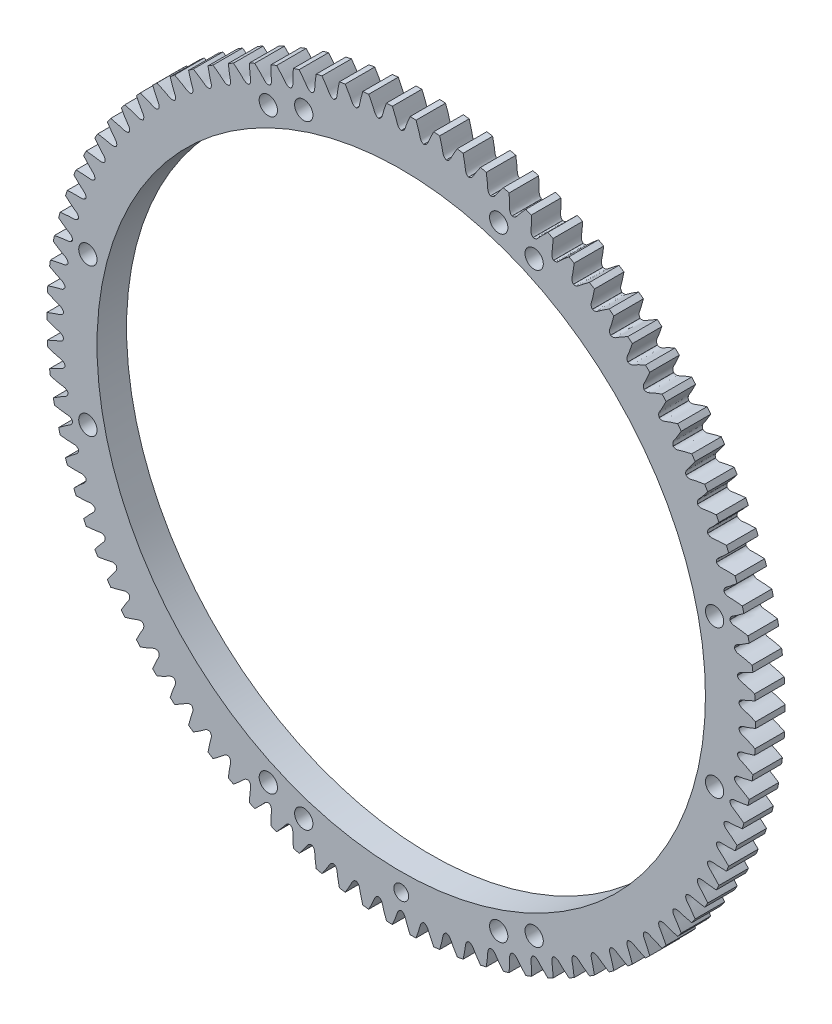
SolidWorks part; units mm, degrees
ref_plane "前视基准面" through (0, 0, 0) normal (0, 0, 1) x (1, 0, 0)
ref_plane "上视基准面" through (0, 0, 0) normal (0, 1, 0) x (1, 0, 0)
ref_plane "右视基准面" through (0, 0, 0) normal (1, 0, 0) x (0, 0, -1)
other "Configuration Table"
sketch "草图1" plane through (0, 0, 0) normal (0, 0, 1) x (1, 0, 0)
  circle A0 centre (0, 0) radius 60
ref_axis "基准轴1" through (0, 0, -66) along (0, 0, 1)
sketch "草图2" plane through (0, 0, 0) normal (0, 0, 1) x (1, 0, 0)
  line L0 (0, 0) -> (0, 60) construction
  circle A0 centre (0, 0) radius 60 construction
  arc A1 (0.01, 57.1863) -> (-0.01, 57.1863) centre (0, 0) ccw
  arc A2 (6.9854, 68.0885) -> (-6.9854, 68.0885) centre (0, 0) ccw
  spline S0 degree 3 poles (0.01, 57.1863) (0.5475, 57.3458) (0.6685, 57.9002) (0.9065, 58.5435) (1.0486, 58.9183) (1.2076, 59.31) (1.3828, 59.7189) (1.5753, 60.1443) (1.7858, 60.5857) (2.0149, 61.0426) (2.2635, 61.5143) (2.5321, 62.0003) (2.8214, 62.5) (3.1321, 63.0126) (3.4648, 63.5376) (3.8201, 64.0743) (4.1987, 64.6219) (4.601, 65.1797) (5.0277, 65.747) (5.4793, 66.3231) (6.1245, 67.1132) (6.6336, 67.6992) (6.9854, 68.0885) knots 0 0 0 0 0.098237 0.127249 0.157953 0.190349 0.224438 0.260219 0.297692 0.336857 0.377715 0.420265 0.464507 0.510441 0.558068 0.607386 0.658397 0.711101 0.765496 0.821584 0.879364 1 1 1 1
  spline S1 degree 3 poles (-0.01, 57.1863) (-0.5475, 57.3458) (-0.6685, 57.9002) (-0.9065, 58.5435) (-1.0486, 58.9183) (-1.2076, 59.31) (-1.3828, 59.7189) (-1.5753, 60.1443) (-1.7858, 60.5857) (-2.0149, 61.0426) (-2.2635, 61.5143) (-2.5321, 62.0003) (-2.8214, 62.5) (-3.1321, 63.0126) (-3.4648, 63.5376) (-3.8201, 64.0743) (-4.1987, 64.6219) (-4.601, 65.1797) (-5.0277, 65.747) (-5.4793, 66.3231) (-6.1245, 67.1132) (-6.6336, 67.6992) (-6.9854, 68.0885) knots 0 0 0 0 0.098237 0.127249 0.157953 0.190349 0.224438 0.260219 0.297692 0.336857 0.377715 0.420265 0.464507 0.510441 0.558068 0.607386 0.658397 0.711101 0.765496 0.821584 0.879364 1 1 1 1
extrude "凸台-拉伸1" add sketch "草图1" along normal blind 5
extrude "切除-拉伸1" cut sketch "草图2" along normal blind 5
pattern_circular "阵列(圆周)1" count 94 every 3.83 about axis through (0, 0, -66) along (0, 0, 1) of "切除-拉伸1"
sketch "草图3" plane through (0, 0, 0) normal (0, 0, 1) x (1, 0, 0)
  circle A0 centre (0, 0) radius 58.75 construction
  dimension "Dn" = 117.5
sketch "草图4" plane through (0, 0, 5) normal (0, 0, 1) x (1, 0, 0)
  line L0 (0, 0) -> (0, 54.5) construction
  line L1 (0, 51.9423) -> (16.5, 51.9423) construction
  line L2 (0, 49.6387) -> (22.5, 49.6387) construction
  line L3 (0, 0) -> (54.5, 0) construction
  line L4 (53.0471, 0) -> (53.0471, 12.5) construction
  circle A0 centre (0, 0) radius 51.5
  circle A1 centre (0, 0) radius 54.5 construction
  circle A2 centre (16.5, 51.9423) radius 1.55
  circle A3 centre (22.5, 49.6387) radius 1.55
  circle A4 centre (53.0471, 12.5) radius 1.55
  circle A5 centre (22.5, -49.6387) radius 1.55
  circle A6 centre (16.5, -51.9423) radius 1.55
  circle A7 centre (53.0471, -12.5) radius 1.55
  circle A8 centre (-16.5, -51.9423) radius 1.55
  circle A9 centre (-22.5, -49.6387) radius 1.55
  circle A10 centre (-53.0471, -12.5) radius 1.55
  circle A11 centre (-53.0471, 12.5) radius 1.55
  circle A12 centre (-22.5, 49.6387) radius 1.55
  circle A13 centre (-16.5, 51.9423) radius 1.55
  dimension "D1" = 103
  dimension "D2" = 109
  dimension "D4" = 3.1
  dimension "D6" = 3.1
  dimension "D8" = 3.1
  dimension "D3" = 16.5
  dimension "D5" = 22.5
  dimension "D7" = 12.5
extrude "切除-拉伸2" cut sketch "草图4" against normal blind 5
sketch "草图5" plane through (0, 0, 5) normal (0, 0, 1) x (1, 0, 0)
  line L0 (0, 0) -> (0, -54.5) construction
  circle A0 centre (0, -54.5) radius 1.25
  dimension "D1" = 2.5
  dimension "D2" = 54.5
extrude "切除-拉伸3" cut sketch "草图5" against normal blind 5
